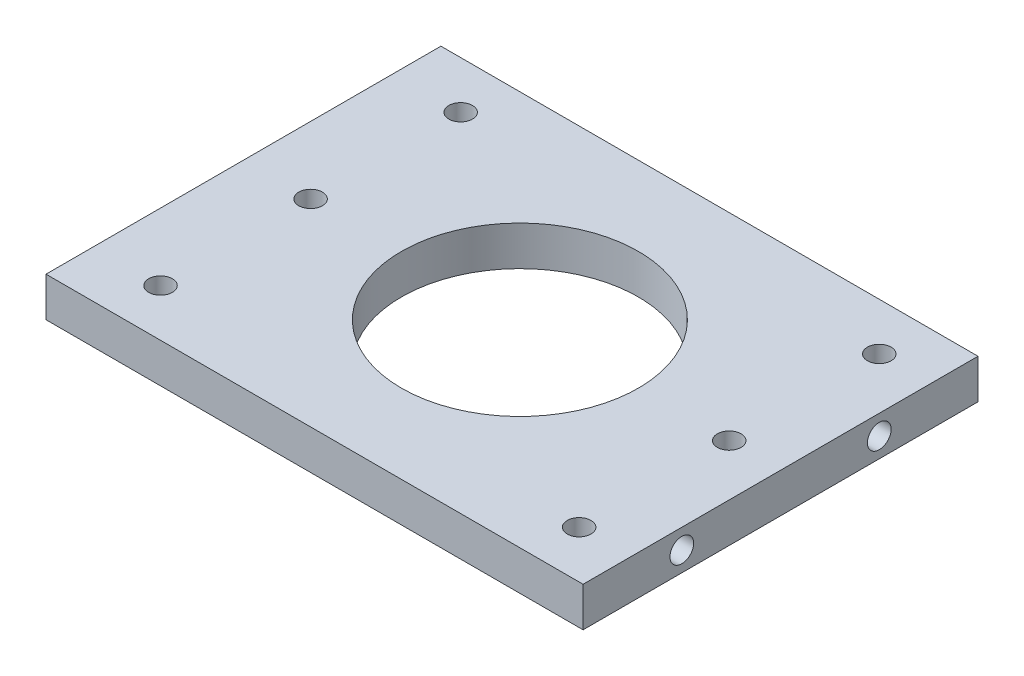
SolidWorks part; units mm, degrees
ref_plane "Plan de face" through (0, 0, 0) normal (0, 0, 1) x (1, 0, 0)
ref_plane "Plan de dessus" through (0, 0, 0) normal (0, 1, 0) x (1, 0, 0)
ref_plane "Plan de droite" through (0, 0, 0) normal (1, 0, 0) x (0, 0, -1)
sketch "Esquisse1" plane through (0, 0, 0) normal (0, 0, 1) x (1, 0, 0)
  line L0 (-15.5, -47.5) -> (52.5, -47.5) construction
  line L5 (-15.5, -45) -> (52.5, -45)
  line L6 (-15.5, -45) -> (-15.5, -50)
  line L7 (-15.5, -50) -> (52.5, -50)
  line L8 (52.5, -45) -> (52.5, -50)
  line L9 (18.5, -45) -> (18.5, -50) construction
  dimension "D1" = 5
  dimension "D2" = 68
extrude "Boss.-Extru.1" add sketch "Esquisse1" along normal blind 50 contours L5 | L7 L8 L5 L6
sketch "Esquisse2" plane through (0, -45, 0) normal (0, 1, 0) x (-1, 0, 0)
  line L0 (15.5, 50) -> (-52.5, 50) construction
  line L1 (15.5, 0) -> (-52.5, 0) construction
  line L7 (-52.5, 50) -> (-52.5, 0) construction
  circle A0 centre (-19.5, 25) radius 15
  circle A1 centre (-46, 44) radius 1.5
  circle A2 centre (-46, 6) radius 1.5
  circle A3 centre (7, 44) radius 1.5
  circle A4 centre (7, 6) radius 1.5
  circle A6 centre (7, 25) radius 1.5
  circle A7 centre (-46, 25) radius 1.5
  point P4 (-46, 24.9989)
  point P21 (7, 25)
  dimension "D6" = 6
  dimension "D2" = 53
  dimension "D3" = 53
  dimension "D4" = 26.5
  dimension "D5" = 26.5
  dimension "D7" = 6
  dimension "D8" = 6
  dimension "D9" = 6
  dimension "D10" = 33
  dimension "D11" = 25
  dimension "D12" = 25
  dimension "D13" = 25
extrude "Enlèv. mat.-Extru.1" cut sketch "Esquisse2" against normal through all
sketch "Esquisse3" plane through (-15.5, 0, 0) normal (-1, 0, 0) x (0, 0, 1)
  line L0 (50, -50) -> (0, -50) construction
  line L1 (0, -45) -> (0, -50) construction
  line L2 (50, -45) -> (50, -50) construction
  circle A0 centre (12.5, -47.5) radius 1.5
  circle A1 centre (37.5, -47.5) radius 1.5
  point P4 (0, 0)
  point P5 (0, 0)
  point P6 (0, 0)
  dimension "D1" = 2.5
  dimension "D2" = 2.5
  dimension "D3" = 12.5
  dimension "D4" = 12.5
extrude "Enlèv. mat.-Extru.2" cut sketch "Esquisse3" against normal blind 10
sketch "Esquisse4" plane through (52.5, 0, 0) normal (1, 0, 0) x (0, 0, -1)
  line L0 (-50, -50) -> (0, -50) construction
  line L1 (-50, -45) -> (-50, -50) construction
  line L2 (0, -45) -> (0, -50) construction
  circle A0 centre (-37.5, -47.5) radius 1.5
  circle A1 centre (-12.5, -47.5) radius 1.5
  dimension "D1" = 2.5
  dimension "D2" = 2.5
  dimension "D3" = 12.5
  dimension "D4" = 12.5
extrude "Enlèv. mat.-Extru.3" cut sketch "Esquisse4" against normal blind 10
